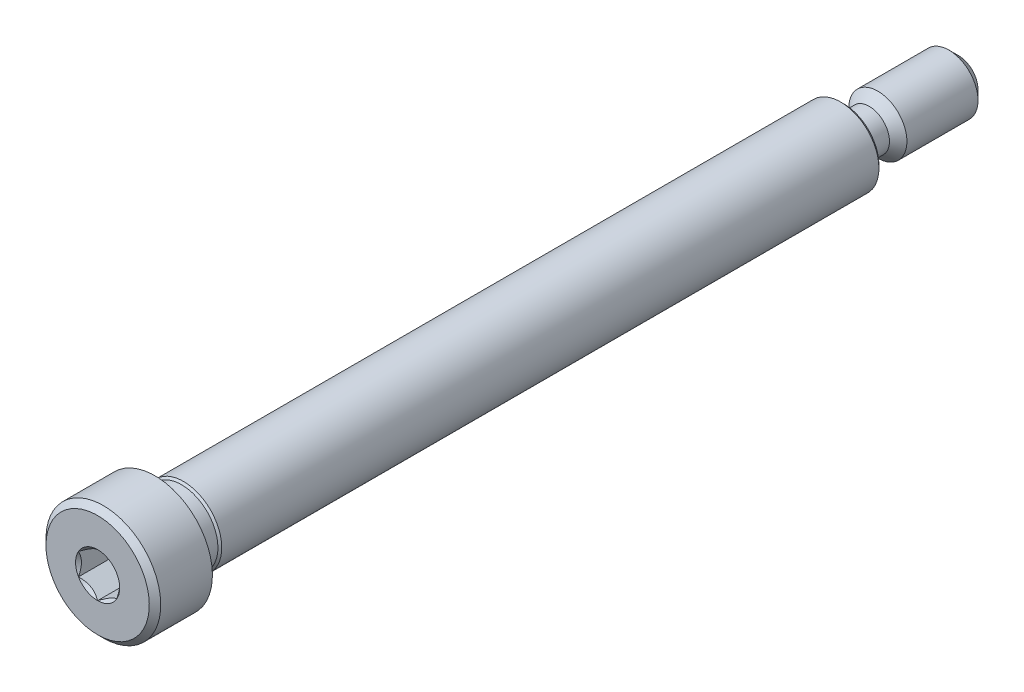
SolidWorks part; units mm, degrees
material "Alloy Steel"
ref_plane "Front Plane" through (0, 0, 0) normal (0, 0, 1) x (1, 0, 0)
ref_plane "Top Plane" through (0, 0, 0) normal (0, 1, 0) x (1, 0, 0)
ref_plane "Right Plane" through (0, 0, 0) normal (1, 0, 0) x (0, 0, -1)
sketch "Sketch2" plane through (0, 0, 0) normal (1, 0, 0) x (0, 0, -1)
  line L0 (-35.7188, 0) -> (35.7188, 0) construction
  line L1 (-35.7188, 0) -> (-35.7188, 4.7625)
  line L2 (-35.7188, 4.7625) -> (-30.9562, 4.7625)
  line L3 (-30.9562, 4.7625) -> (-30.9563, 3.175)
  line L4 (-30.9563, 3.175) -> (26.1938, 3.175)
  line L5 (26.1938, 2.413) -> (35.7188, 2.413)
  line L6 (35.7188, 2.413) -> (35.7188, 0)
  line L7 (35.6526, 2.5276) -> (36.1818, 1.611) construction
  line L8 (36.1818, 1.611) -> (36.7109, 2.5276) construction
  line L9 (36.7109, 2.5276) -> (35.6526, 2.5276) construction
  line L10 (35.7188, 2.413) -> (36.6448, 2.413) construction
  line L11 (36.1818, 2.5276) -> (36.1818, 2.413) construction
  line L12 (36.1818, 2.413) -> (36.1818, 1.7256) construction
  line L13 (36.1818, 1.7256) -> (36.1818, 1.611) construction
  line L14 (36.1156, 1.7256) -> (36.2479, 1.7256)
  line L15 (35.6857, 2.4703) -> (36.6779, 2.4703)
  line L16 (36.2479, 1.7256) -> (36.6779, 2.4703)
  line L17 (36.1156, 1.7256) -> (35.6857, 2.4703)
  line L18 (35.7188, 0) -> (35.7188, -2.413) construction
  line L19 (26.1938, -3.175) -> (26.1938, 0) construction
  line L20 (26.1938, 0) -> (26.1938, 3.175) construction
  line L21 (-35.7188, 0) -> (-35.7188, -4.7625) construction
  point P11 (-28.594, 3.175)
  point P12 (33.0729, -2.413)
  point P22 (36.1818, 2.4703)
  point P23 (25.7175, 0)
  point P25 (-25.7175, 0)
  point P26 (-30.9562, -4.7625)
  point P29 (26.1938, -3.175)
  dimension "Head Height" = 4.7625
  dimension "Shoulder Diameter" = 6.35
  dimension "Screw Size Decimal Equivalent" = 4.826
  dimension "Thread Length" = 9.525
  dimension "Head Diameter" = 9.525
  dimension "Undercut Length" = 2.3622
  dimension "Pitch" = 1.0583
  dimension "D2" = 0.1323
  dimension "D1" = 2.6458
  dimension "D3" = 10.0013
  dimension "D4" = 10.0012
  dimension "Shoulder Length" = 57.15
sketch "Sketch3" plane through (0, 0, 0) normal (0, 0, 1) x (1, 0, 0)
  line L1 (0, 1.8331) -> (-1.5875, 0.9165)
  line L2 (-1.5875, 0.9165) -> (-1.5875, -0.9165)
  line L3 (-1.5875, -0.9165) -> (0, -1.8331)
  line L4 (0, -1.8331) -> (1.5875, -0.9165)
  line L5 (1.5875, -0.9165) -> (1.5875, 0.9165)
  line L6 (1.5875, 0.9165) -> (0, 1.8331)
  circle A0 centre (0, 0) radius 1.5875 construction
  dimension "Drive Size" = 3.175
sketch "Sketch4" plane through (0, 0, 0) normal (1, 0, 0) x (0, 0, -1)
  line L0 (-30.9562, 4.7625) -> (-35.2425, 4.7625)
  line L1 (-35.2425, 4.7625) -> (-35.7188, 4.2862)
  line L2 (-30.9562, 4.7625) -> (-30.9563, 3.175)
  line L3 (-30.9563, 3.175) -> (-30.7975, 3.0162)
  line L4 (-30.7975, 3.0162) -> (-28.7528, 3.0162)
  line L5 (-28.7528, 3.0162) -> (-28.594, 3.175)
  line L6 (-30.9563, 3.175) -> (26.1938, 3.175) construction
  line L7 (-35.7188, 0) -> (35.7188, 0) construction
  line L8 (-28.594, 3.175) -> (25.9397, 3.175)
  line L9 (25.9397, 3.175) -> (26.1938, 2.921)
  line L10 (26.1938, 2.921) -> (26.1938, 0)
  line L11 (26.1938, 3.175) -> (26.1938, 2.921) construction
  line L12 (26.1938, 2.921) -> (26.1938, 2.667) construction
  line L13 (26.1938, 2.667) -> (26.1938, 2.413) construction
  line L14 (-35.7188, 4.2862) -> (-35.7188, 0)
  line L15 (-35.7188, 4.7625) -> (-30.9562, 4.7625) construction
  line L16 (-35.7188, 0) -> (26.1938, 0)
  dimension "D1" = 45
  dimension "D2" = 6.0325
  dimension "D3" = 45
  dimension "D4" = 45
  dimension "D5" = 8.5725
revolve "Revolve1" add sketch "Sketch4" angle 360 about L16
sketch "Sketch5" plane through (0, 0, 35.7188) normal (0, 0, 1) x (1, 0, 0)
  line L0 (1.5875, 0.9165) -> (0, 1.8331) construction
  line L1 (1.5875, -0.9165) -> (1.5875, 0.9165) construction
  line L2 (0, -1.8331) -> (1.5875, -0.9165) construction
  line L3 (-1.5875, -0.9165) -> (0, -1.8331) construction
  line L4 (-1.5875, 0.9165) -> (-1.5875, -0.9165) construction
  line L5 (0, 1.8331) -> (-1.5875, 0.9165) construction
  line L6 (1.5875, 0.9165) -> (0, 1.8331)
  line L7 (1.5875, -0.9165) -> (1.5875, 0.9165)
  line L8 (0, -1.8331) -> (1.5875, -0.9165)
  line L9 (-1.5875, -0.9165) -> (0, -1.8331)
  line L10 (-1.5875, 0.9165) -> (-1.5875, -0.9165)
  line L11 (0, 1.8331) -> (-1.5875, 0.9165)
extrude "Cut-Extrude1" cut sketch "Sketch5" against normal blind 3.5719
sketch "Sketch6" plane through (0, 0, 35.7188) normal (0, 0, 1) x (1, 0, 0)
  circle A0 centre (0, 0) radius 1.8331
extrude "Cut-Extrude4" cut sketch "Sketch6" against normal blind 3.5719 draft 45
sketch "Sketch7" plane through (0, 0, 0) normal (1, 0, 0) x (0, 0, -1)
  line L0 (26.1938, 2.413) -> (34.925, 2.413)
  line L1 (26.1938, 2.413) -> (35.7188, 2.413) construction
  line L2 (34.925, 2.413) -> (35.7188, 1.6192)
  line L3 (35.7188, 2.413) -> (35.7188, 0) construction
  line L4 (35.7188, 1.6192) -> (35.7188, 0)
  line L5 (35.7188, 0) -> (26.1938, 0)
  line L6 (26.1938, -2.921) -> (26.1938, 2.921) construction
  line L7 (26.1938, 0) -> (26.1938, 2.413)
  dimension "D1" = 45
  dimension "D2" = 0.7938
revolve "Revolve2" add sketch "Sketch7" angle 360 about L5
sketch "Sketch10" plane through (0, 0, 0) normal (1, 0, 0) x (0, 0, -1)
  line L0 (26.9176, 1.6891) -> (28.302, 1.6891)
  line L1 (28.302, 1.6891) -> (29.7879, 3.175)
  line L2 (29.7879, 3.175) -> (26.1938, 3.175)
  line L3 (26.1938, 3.175) -> (26.1938, 2.413)
  line L4 (26.1938, -2.921) -> (26.1938, 2.921) construction
  line L5 (35.7188, 0) -> (26.1938, 0) construction
  line L6 (-35.7188, 0) -> (35.7188, 0) construction
  arc A0 (26.1938, 2.413) -> (26.9176, 1.6891) centre (26.9177, 2.413) ccw
  dimension "Flat OD" = 3.3782
  dimension "Flat" = 2.1082
  dimension "D3" = 45
revolve "Cut-Revolve1" cut sketch "Sketch10" angle 360 about L5
sketch "Sketch8" [suppressed] plane through (0, 0, -35.7188) normal (0, 0, -1) x (-1, 0, 0)
  circle A0 centre (0, 0) radius 2.413 construction
  circle A1 centre (0, 0) radius 2.413
curve "Helix/Spiral1" [suppressed] pitch 1.0583 height 10.5833 turns 10
sketch "Sketch9" [suppressed] plane through (0, 0, 0) normal (1, 0, 0) x (0, 0, -1)
  line L0 (36.1156, 1.7256) -> (36.2479, 1.7256) construction
  line L1 (36.2479, 1.7256) -> (36.6779, 2.4703) construction
  line L2 (35.6857, 2.4703) -> (36.6779, 2.4703) construction
  line L3 (36.1156, 1.7256) -> (35.6857, 2.4703) construction
  line L4 (36.1156, 1.7256) -> (36.2479, 1.7256)
  line L5 (36.2479, 1.7256) -> (36.6779, 2.4703)
  line L6 (35.6857, 2.4703) -> (36.6779, 2.4703)
  line L7 (36.1156, 1.7256) -> (35.6857, 2.4703)
ref_plane "Plane1" [suppressed] through (0, 0, -28.302) normal (0, 0, 1) x (1, 0, 0)
split "Split1" [suppressed] bodies to split 138
sweep "Cut-Sweep1" [suppressed] cut profiles "Sketch9" path "Helix/Spiral1"
combine bodies "Combine1" [suppressed] operation type add bodies to combine 141 139
sketch "Sketch11" [suppressed] plane through (0, 0, 35.7188) normal (0, 0, 1) x (1, 0, 0)
  line L0 (-0.0687, 4.7625) -> (0.0687, 4.7625)
  line L1 (0.0687, 4.7625) -> (0, 4.6434)
  line L2 (0, 0) -> (0, 4.7625) construction
  line L3 (0, 4.6434) -> (-0.0687, 4.7625)
  line L4 (0, 0) -> (4.7625, 0) construction
  circle A0 centre (0, 0) radius 4.7625 construction
  point P6 (0, 4.7625)
  dimension "D1" = 9.2869
  dimension "D2" = 60
  dimension "D3" = 0.1375
sketch "Sketch12" [suppressed] plane through (0, 0, 0) normal (1, 0, 0) x (0, 0, -1)
  line L0 (-35.7188, 4.6434) -> (-32.4343, 4.6434)
  line L1 (-32.0278, 5.0499) -> (-32.0278, 4.7625) construction
  line L2 (-35.7188, 4.7625) -> (-30.9562, 4.7625) construction
  arc A0 (-32.4343, 4.6434) -> (-32.0278, 5.0499) centre (-32.4343, 5.0499) ccw
  point P11 (-32.1469, 4.7625)
  dimension "D1" = 1.1906
sweep "Cut-Sweep2" [suppressed] cut profiles "Sketch11" path "Sketch12"
pattern_circular "CirPattern1" [suppressed] count 76 over 360 about axis through (0, 0, 35.7188) along (0, 0, -1) of bodies 143
equation "\"D2@Sketch2\" = \"Pitch@Sketch2\" / 8"
equation "\"D1@Sketch2\"=\"Pitch@Sketch2\"*2.5"
equation "\"D2@Sketch4\"=\"Shoulder Diameter@Sketch2\"*0.95"
equation "\"D5@Sketch4\"=\"Head Diameter@Sketch2\"*0.9"
equation "\"D1@Cut-Extrude1\"=\"Head Height@Sketch2\"*0.75"
equation "\"D1@Cut-Extrude4\"=\"D1@Cut-Extrude1\""
equation "\"D2@Sketch7\"=\"pitch@sketch2\"*0.75"
equation "\"D3@Helix/Spiral1\"=\"Thread Length@Sketch2\"+\"Pitch@Sketch2\""
equation "\"D4@Helix/Spiral1\"=\"Pitch@Sketch2\""
equation "\"D1@Sketch11\"=\"Head Diameter@Sketch2\"*0.975"
equation "\"D1@Sketch12\"=\"Head Height@Sketch2\"*0.25"
equation "\"D1@CirPattern1\"=\"Head Diameter@Sketch2\" * 3.14 / \"D3@Sketch11\" * 0.35"
equation "\"D3@Sketch2\"=\"Thread Length@Sketch2\"*1.05"
equation "\"D4@Sketch2\"=\"D3@Sketch2\""
